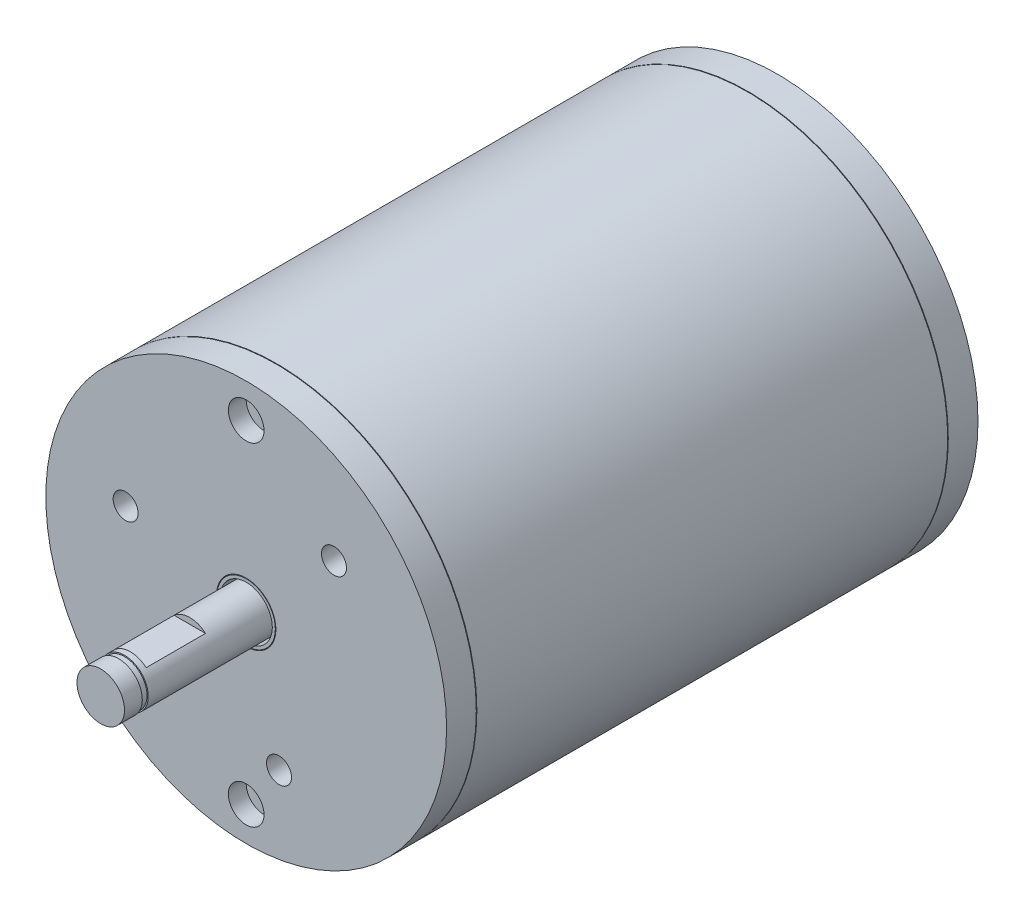
SolidWorks part; units mm, degrees
ref_plane "Front Plane" through (0, 0, 0) normal (0, 0, 1) x (1, 0, 0)
ref_plane "Top Plane" through (0, 0, 0) normal (0, 1, 0) x (1, 0, 0)
ref_plane "Right Plane" through (0, 0, 0) normal (1, 0, 0) x (0, 0, -1)
sketch "Sketch1" plane through (0, 0, 0) normal (0, 0, 1) x (1, 0, 0)
  circle A0 centre (0, 0) radius 33.75
  dimension "D1" = 67.5
extrude "Boss-Extrude1" add sketch "Sketch1" along normal blind 5
sketch "Sketch2" plane through (0, 0, 5) normal (0, 0, 1) x (1, 0, 0)
  circle A0 centre (0, 0) radius 33.6
  dimension "D1" = 67.2
extrude "Boss-Extrude2" add sketch "Sketch2" along normal blind 0.1
sketch "Sketch3" plane through (0, 0, 5.1) normal (0, 0, 1) x (1, 0, 0)
  circle A0 centre (0, 0) radius 33.75
  dimension "D1" = 67.5
extrude "Boss-Extrude3" add sketch "Sketch3" along normal blind 79.3
sketch "Sketch4" plane through (0, 0, 84.4) normal (0, 0, 1) x (1, 0, 0)
  circle A0 centre (0, 0) radius 33.6
  dimension "D1" = 67.2
extrude "Boss-Extrude4" add sketch "Sketch4" along normal blind 0.1
sketch "Sketch5" plane through (0, 0, 84.5) normal (0, 0, 1) x (1, 0, 0)
  circle A0 centre (0, 0) radius 33.75
  dimension "D1" = 67.5
extrude "Boss-Extrude5" add sketch "Sketch5" along normal blind 5
sketch "Sketch6" plane through (0, 0, 89.5) normal (0, 0, 1) x (1, 0, 0)
  circle A0 centre (0, 0) radius 21 construction
  circle A1 centre (14.3312, 15.3498) radius 2.1 construction
  circle A2 centre (6.1277, -20.0861) radius 2.1 construction
  circle A3 centre (-20.4589, 4.7363) radius 2.1 construction
  circle A4 centre (0, 0) radius 5
  dimension "D1" = 42
  dimension "D2" = 4.2
  dimension "D4" = 10
  dimension "D3" = 3
extrude "Cut-Extrude1" cut sketch "Sketch6" against normal blind 5
sketch "Sketch7" plane through (0, 0, 84.5) normal (0, 0, 1) x (1, 0, 0)
  circle A0 centre (0, 0) radius 4.9
  circle A1 centre (0, 0) radius 4.4
  dimension "D1" = 9.8
  dimension "D2" = 0.5
extrude "Boss-Extrude6" add sketch "Sketch7" along normal blind 5
sketch "Sketch8" plane through (0, 0, 84.5) normal (0, 0, 1) x (1, 0, 0)
  circle A0 centre (0, 0) radius 4
  dimension "D1" = 8
extrude "Boss-Extrude7" add sketch "Sketch8" along normal blind 24.5
sketch "Sketch9" plane through (0, 0, 0) normal (0, 0, -1) x (-1, 0, 0)
  circle A0 centre (0, 0) radius 15
  dimension "D1" = 30
extrude "Boss-Extrude8" add sketch "Sketch9" along normal blind 9.91
sketch "Sketch10" plane through (0, 0, 89.5) normal (0, 0, 1) x (1, 0, 0)
  circle A0 centre (0, 0) radius 21 construction
  circle A1 centre (14.7831, 14.9151) radius 1.75 construction
  circle A2 centre (5.5253, -20.2601) radius 1.75 construction
  circle A3 centre (-20.3084, 5.345) radius 1.75 construction
  dimension "D1" = 42
  dimension "D2" = 3.5
  dimension "D3" = 3
hole_wizard "M5 Tapped Hole1" positions "3DSketch1" profile "Sketch11" tap size "M5" standard "ISO"
sketch3d "3DSketch1"
  point P0 (-20.3084, 5.345, 89.5)
  point P3 (14.7831, 14.9151, 89.5)
  point P6 (5.5253, -20.2601, 89.5)
sketch "Sketch11" plane through (-20.3084, 5.345, 89.5) normal (1, 0, 0) x (0, -1, 0)
  line L0 (0, 0) -> (0, 6.2618)
  line L1 (0, 6.2618) -> (2.1, 5)
  line L2 (2.1, 5) -> (2.1, 0)
  line L5 (2.1, 0) -> (0, 0)
  line L10 (0, 6.2618) -> (-2.1, 5) construction
  line L11 (0, -6.35) -> (0, 107.95) construction
  dimension "Tap Drill Dia." = 4.2
  dimension "Tap Drill Depth" = 5
  dimension "Drill Angle" = 118
cosmetic thread "Hole Thread1" parameters "D1"=5, "D2"=5
cosmetic thread "Hole Thread2" parameters "D1"=5, "D2"=5
cosmetic thread "Hole Thread3" parameters "D1"=5, "D2"=5
ref_plane "Plane1" through (0, 4, 0) normal (0, 1, 0) x (1, 0, 0)
sketch "Sketch12" plane through (0, 4, 0) normal (0, 1, 0) x (1, 0, 0)
  line L1 (-4, -109) -> (4, -109)
  line L2 (-4, -109) -> (-4, -99)
  line L3 (-4, -99) -> (4, -99)
  line L4 (4, -109) -> (4, -99)
  dimension "D1" = 10
extrude "Cut-Extrude2" cut sketch "Sketch12" against normal blind 1 contours L4 L3 L2 L1
sketch "Sketch13" plane through (0, 0, 109) normal (0, 0, 1) x (1, 0, 0)
  circle A0 centre (0, 0) radius 4
extrude "Boss-Extrude9" add sketch "Sketch13" along normal blind 1
sketch "Sketch14" plane through (0, 0, 110) normal (0, 0, 1) x (1, 0, 0)
  circle A0 centre (0, 0) radius 3.8
  dimension "D1" = 7.6
extrude "Boss-Extrude10" add sketch "Sketch14" along normal blind 1
sketch "Sketch15" plane through (0, 0, 111) normal (0, 0, 1) x (1, 0, 0)
  circle A0 centre (0, 0) radius 4
  dimension "D1" = 8
extrude "Boss-Extrude11" add sketch "Sketch15" along normal blind 3
sketch "Sketch16" plane through (0, 0, 89.5) normal (0, 0, 1) x (1, 0, 0)
  circle A0 centre (0, 28) radius 3
  circle A1 centre (0, -28) radius 3
  dimension "D1" = 6
  dimension "D2" = 6
  dimension "D3" = 28
  dimension "D4" = 28
extrude "Cut-Extrude3" cut sketch "Sketch16" against normal blind 3
ref_plane "Plane2" through (0, 0, 110.5) normal (0, 0, 1) x (1, 0, 0)
ref_point "Point1"
ref_point "Point2"
ref_axis "Axis1" through (0, 0, -29.5916) along (0, 0, 1)
